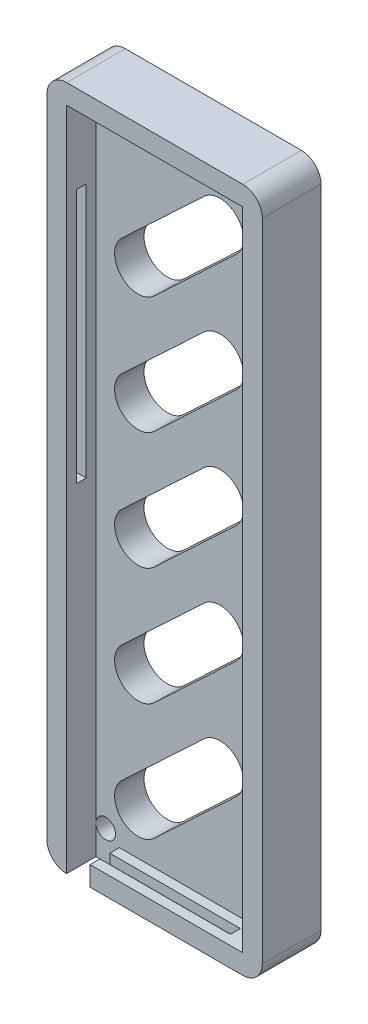
SolidWorks part; units mm, degrees
ref_plane "前视基准面" through (0, 0, 0) normal (0, 0, 1) x (1, 0, 0)
ref_plane "上视基准面" through (0, 0, 0) normal (0, 1, 0) x (1, 0, 0)
ref_plane "右视基准面" through (0, 0, 0) normal (1, 0, 0) x (0, 0, -1)
sketch "草图1" plane through (0, 0, 0) normal (0, 0, 1) x (1, 0, 0)
  line L1 (-2.8217, 18.8054) -> (8.1783, 18.8054)
  line L2 (-2.8217, 18.8054) -> (-2.8217, -16.1946)
  line L3 (-2.8217, -16.1946) -> (8.1783, -16.1946)
  line L4 (8.1783, 18.8054) -> (8.1783, -16.1946)
  dimension "D1" = 11
  dimension "D2" = 35
extrude "凸台-拉伸2" add sketch "草图1" along normal blind 3 contours L2 L1 L4 L3
sketch "草图2" plane through (0, 0, 3) normal (0, 0, 1) x (1, 0, 0)
  line L0 (-1.8217, 17.8054) -> (7.1783, 17.8054)
  line L1 (-1.8217, 17.8054) -> (-1.8217, -15.1946)
  line L2 (-1.8217, -15.1946) -> (7.1783, -15.1946)
  line L3 (7.1783, 17.8054) -> (7.1783, -15.1946)
  line L5 (-2.8217, 18.8054) -> (8.1783, 18.8054) construction
  line L6 (-2.8217, 18.8054) -> (-2.8217, -16.1946) construction
  line L7 (-2.8217, -16.1946) -> (8.1783, -16.1946) construction
  line L8 (8.1783, 18.8054) -> (8.1783, -16.1946) construction
  dimension "D1" = 1
  dimension "D2" = 1
  dimension "D3" = 1
  dimension "D4" = 1
extrude "切除-拉伸1" cut sketch "草图2" against normal blind 1.5
sketch "草图4" plane through (0, 0, 3) normal (0, 0, 1) x (1, 0, 0)
  line L0 (-2.8217, -16.1946) -> (8.1783, -16.1946) construction
  line L1 (-1.8217, -15.1946) -> (-0.6217, -15.1946)
  line L2 (-1.8217, -15.1946) -> (-1.8217, -16.1946)
  line L3 (-1.8217, -16.1946) -> (-0.6217, -16.1946)
  line L4 (-0.6217, -15.1946) -> (-0.6217, -16.1946)
  dimension "D1" = 1.2
extrude "切除-拉伸4" cut sketch "草图4" against normal up to surface (1.5 mm away) up to face at (2.6783, 1.3054, 1.5)
fillet "圆角2" radius 1 4 edges at (-2.8217, 18.8054, 1.5) (8.1783, 18.8054, 1.5) (8.1783, -16.1946, 1.5) (-2.8217, -16.1946, 1.5)
sketch "草图6" plane through (0, 17.8054, 0) normal (0, -1, 0) x (1, 0, 0)
  line L1 (-0.575, 2.5) -> (6.1897, 2.5)
  line L2 (-0.575, 2.5) -> (-0.575, 1.7889)
  line L3 (-0.575, 1.7889) -> (6.1897, 1.7889)
  line L4 (6.1897, 2.5) -> (6.1897, 1.7889)
extrude "切除-拉伸6" cut sketch "草图6" against normal blind 0.5
sketch "草图7" plane through (-1.8217, 0, 0) normal (1, 0, 0) x (0, 0, -1)
  line L1 (-2.5, 13.8139) -> (-1.996, 13.8139)
  line L2 (-2.5, 13.8139) -> (-2.5, 0.8071)
  line L3 (-2.5, 0.8071) -> (-1.996, 0.8071)
  line L4 (-1.996, 13.8139) -> (-1.996, 0.8071)
extrude "切除-拉伸7" cut sketch "草图7" against normal blind 0.5
sketch "草图8" plane through (7.1783, 0, 0) normal (-1, 0, 0) x (0, 0, 1)
  line L1 (2.5047, 15.729) -> (1.9867, 15.729)
  line L2 (2.5047, 15.729) -> (2.5047, -12.0365)
  line L3 (2.5047, -12.0365) -> (1.9867, -12.0365)
  line L4 (1.9867, 15.729) -> (1.9867, -12.0365)
  point P6 (0, 0)
  point P7 (0, 0)
  point P8 (0, 0)
extrude "切除-拉伸8" cut sketch "草图8" against normal blind 0.5
sketch "草图10" plane through (0, -15.1946, 0) normal (0, 1, 0) x (1, 0, 0)
  line L1 (6.0494, -1.9905) -> (-0.7996, -1.9905)
  line L2 (6.0494, -1.9905) -> (6.0494, -2.4974)
  line L3 (6.0494, -2.4974) -> (-0.7996, -2.4974)
  line L4 (-0.7996, -1.9905) -> (-0.7996, -2.4974)
extrude "切除-拉伸9" cut sketch "草图10" against normal blind 0.5
sketch "草图11" plane through (0, 0, 0) normal (0, 0, -1) x (-1, 0, 0)
  line L0 (-4.5195, 14.9075) -> (-0.3314, 10.9751) construction
  line L1 (-3.7001, 15.7803) -> (0.4881, 11.8479)
  line L2 (-5.339, 14.0347) -> (-1.1509, 10.1024)
  line L3 (-5.339, 8.0347) -> (-1.1509, 4.1024)
  line L4 (-3.7001, 9.7803) -> (0.4881, 5.8479)
  line L5 (-4.5195, 8.9075) -> (-0.3314, 4.9751) construction
  line L6 (-5.339, 2.0347) -> (-1.1509, -1.8976)
  line L7 (-3.7001, 3.7803) -> (0.4881, -0.1521)
  line L8 (-4.5195, 2.9075) -> (-0.3314, -1.0249) construction
  line L9 (-5.339, -3.9653) -> (-1.1509, -7.8976)
  line L10 (-3.7001, -2.2197) -> (0.4881, -6.1521)
  line L11 (-4.5195, -3.0925) -> (-0.3314, -7.0249) construction
  line L12 (-5.339, -9.9653) -> (-1.1509, -13.8976)
  line L13 (-3.7001, -8.2197) -> (0.4881, -12.1521)
  line L14 (-4.5195, -9.0925) -> (-0.3314, -13.0249) construction
  arc A0 (-3.7001, 15.7803) -> (-5.339, 14.0347) centre (-4.5195, 14.9075) ccw
  arc A1 (-1.1509, 10.1024) -> (0.4881, 11.8479) centre (-0.3314, 10.9751) ccw
  arc A2 (-3.7001, 9.7803) -> (-5.339, 8.0347) centre (-4.5195, 8.9075) ccw
  arc A3 (-1.1509, 4.1024) -> (0.4881, 5.8479) centre (-0.3314, 4.9751) ccw
  arc A4 (-3.7001, 3.7803) -> (-5.339, 2.0347) centre (-4.5195, 2.9075) ccw
  arc A5 (-1.1509, -1.8976) -> (0.4881, -0.1521) centre (-0.3314, -1.0249) ccw
  arc A6 (-3.7001, -2.2197) -> (-5.339, -3.9653) centre (-4.5195, -3.0925) ccw
  arc A7 (-1.1509, -7.8976) -> (0.4881, -6.1521) centre (-0.3314, -7.0249) ccw
  arc A8 (-3.7001, -8.2197) -> (-5.339, -9.9653) centre (-4.5195, -9.0925) ccw
  arc A9 (-1.1509, -13.8976) -> (0.4881, -12.1521) centre (-0.3314, -13.0249) ccw
  point P2 (-2.4255, 12.9413)
  point P9 (-2.4255, 6.9413)
  point P16 (-2.4255, 0.9413)
  point P23 (-2.4255, -5.0587)
  point P30 (-2.4255, -11.0587)
extrude "切除-拉伸11" cut sketch "草图11" against normal up to next
sketch "草图13" plane through (0, 0, 3) normal (0, 0, 1) x (1, 0, 0)
  circle A0 centre (-1.3217, 17.3054) radius 0.5
  circle A1 centre (6.6783, 17.3054) radius 0.5
  circle A2 centre (6.6783, -14.6946) radius 0.5
  circle A3 centre (-1.3217, -14.6946) radius 0.5
  point P12 (-1.8217, 20.2054)
extrude "切除-拉伸12" cut sketch "草图13" against normal offset from surface (2.8 mm away) 0.2 up to face at (2.4255, 0.9413, 0)
